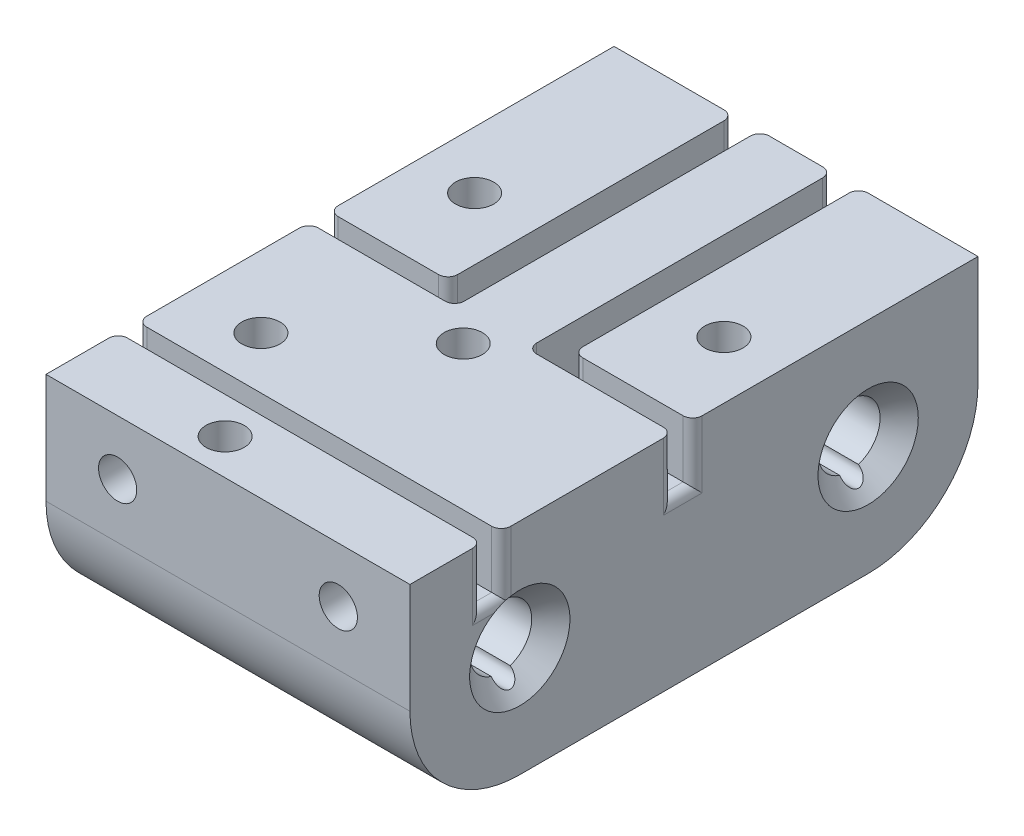
SolidWorks part; units mm, degrees
ref_plane "Front Plane" through (0, 0, 0) normal (0, 0, 1) x (1, 0, 0)
ref_plane "Top Plane" through (0, 0, 0) normal (0, 1, 0) x (1, 0, 0)
ref_plane "Right Plane" through (0, 0, 0) normal (1, 0, 0) x (0, 0, -1)
sketch "Sketch1" plane through (0, 0, 0) normal (1, 0, 0) x (0, 0, -1)
  line L0 (-18.235, 0) -> (18.235, 0)
  line L1 (0, 0) -> (0, -11.9416) construction
  line L3 (-29.735, 11.5) -> (29.735, 11.5)
  line L4 (-29.735, 11.5) -> (-29.735, 0)
  line L5 (-29.735, 0) -> (29.735, 0)
  line L6 (29.735, 11.5) -> (29.735, 0)
  circle A0 centre (-18.235, 0) radius 3.25
  circle A2 centre (-18.235, 0) radius 11.5
  circle A3 centre (18.235, 0) radius 3.25
  circle A4 centre (18.235, 0) radius 11.5
  point P2 (0, 0)
  point P14 (0, 0)
  point P15 (0, 0)
  dimension "D2" = 6.5
  dimension "D3" = 23
  dimension "D1" = 36.47
  dimension "D4" = 59.47
extrude "Boss-Extrude1" add sketch "Sketch1" along normal blind 38.1 contours A4 L5 A3 | A4 L5 A3 | L5 A2 A0 | L5 A2 A0 | L0 L5 A4 L3 A2 | L3 A4 L6 | A2 L3 L4 region at (0, 5.1847, 18.235) region at (0, -5.1847, 18.235) region at (0, 6.6031, 0) region at (0, 8.9313, 27.1663) region at (0, 5.1847, -18.235) region at (0, -5.1847, -18.235) region at (0, 8.9313, -27.1663)
ref_plane "Plane1" through (0, -11.5, 0) normal (0, -1, 0) x (-1, 0, 0)
sketch "Sketch2" plane through (0, -11.5, 0) normal (0, -1, 0) x (-1, 0, 0)
  line L0 (-38.1, 29.735) -> (-38.1, 6.735) construction
  line L1 (-38.1, 18.235) -> (0, 18.235)
  line L2 (-38.1, 18.235) -> (-38.1, -18.235)
  line L3 (-38.1, -18.235) -> (0, -18.235)
  line L4 (0, 18.235) -> (0, -18.235)
  line L5 (0, -29.735) -> (0, -6.735) construction
extrude "Boss-Extrude2" add sketch "Sketch2" against normal up to next
sketch "Sketch3" plane through (0, 11.5, 0) normal (0, 1, 0) x (1, 0, 0)
  line L0 (0, 29.735) -> (38.1, 29.735) construction
  line L1 (0, -0.14) -> (12.5, -0.14)
  line L2 (12.5, -0.14) -> (12.5, 29.735)
  line L3 (15.26, 29.735) -> (15.26, -2.21)
  line L4 (15.26, -2.21) -> (0, -2.21)
  line L5 (19.05, -12.535) -> (19.05, 29.735) construction
  line L6 (0, -1.1775) -> (38.1, -1.1775) construction
  line L7 (22.84, -2.21) -> (38.1, -2.21)
  line L8 (22.84, 29.735) -> (22.84, -2.21)
  line L9 (25.6, -0.14) -> (25.6, 29.735)
  line L10 (38.1, -0.14) -> (25.6, -0.14)
  line L11 (0, 29.735) -> (38.1, 29.735)
  line L12 (0, 29.735) -> (0, -12.535)
  line L13 (0, -12.535) -> (38.1, -12.535)
  line L14 (38.1, 29.735) -> (38.1, -12.535)
  line L15 (0, -2.21) -> (0, -12.535) construction
  line L16 (38.1, 29.735) -> (0, 29.735) construction
  line L17 (0, -29.735) -> (0, 29.735) construction
  line L18 (38.1, -29.735) -> (38.1, 29.735) construction
  line L19 (0, -20.1775) -> (38.1, -20.1775)
  line L20 (0, -20.1775) -> (0, -22.1775)
  line L21 (0, -22.1775) -> (38.1, -22.1775)
  line L22 (38.1, -20.1775) -> (38.1, -22.1775)
  line L23 (0, -21.1775) -> (38.1, -21.1775) construction
  line M5 (0, 29.735) -> (0, -29.735)
  line M7 (38.1, -29.735) -> (38.1, 29.735)
  line M8 (38.1, 29.735) -> (0, 29.735)
  dimension "D1" = 10.325
  dimension "D2" = 12.395
  dimension "D3" = 12.5
  dimension "D4" = 15.26
  dimension "D5" = 1.0375
  dimension "D6" = 38.1
  dimension "D7" = 42.27
  dimension "D8" = 2
  dimension "D9" = 20
extrude "Cut-Extrude1" cut sketch "Sketch3" against normal blind 6 contours L10 L9 L8 L7 M7 M8 | L4 L3 L2 L1 M8 M5 | L19 L22 L21 L20 region at (6.25, 11.5, 0.494) region at (24.22, 11.5, -29.381)
sketch "Sketch4" plane through (0, 11.5, 0) normal (0, 1, 0) x (1, 0, 0)
  line L0 (19.05, 29.735) -> (19.05, -10.265) construction
  line L1 (0, 29.735) -> (38.1, 29.735)
  line L2 (0, 29.735) -> (0, -10.265)
  line L3 (0, -10.265) -> (38.1, -10.265)
  line L4 (38.1, 29.735) -> (38.1, -10.265)
  line L5 (0, -29.735) -> (15, -29.735)
  line L6 (0, -29.735) -> (0, -14.735)
  line L7 (0, -14.735) -> (15, -14.735)
  line L8 (15, -29.735) -> (15, -14.735)
  line L9 (0, -0.14) -> (0, 29.735) construction
  line L10 (38.1, -29.735) -> (0, -29.735) construction
  circle A0 centre (19.05, -5.105) radius 2
  circle A1 centre (6, 9.135) radius 2
  circle A2 centre (32.1, 9.135) radius 2
  circle A3 centre (15, -25.985) radius 2
  circle A4 centre (7.5, -14.735) radius 2
  point P20 (0, 29.735)
  point P22 (1.009, 28.3457)
  point P24 (0, -29.735)
  point P27 (0, -29.735)
  dimension "D4" = 4
  dimension "D9" = 4
  dimension "D10" = 4
  dimension "D1" = 38.1
  dimension "D2" = 5.16
  dimension "D3" = 6
  dimension "D5" = 19.4
  dimension "D6" = 40
  dimension "D7" = 15
  dimension "D8" = 15
  dimension "D11" = 3.75
extrude "Cut-Extrude2" cut sketch "Sketch4" against normal blind 5 contours A1 | A2 | L7 A4 | L7 A4 | L8 A3 | L8 A3 | A0 region at (14.1512, 11.5, 25.985) region at (15.8488, 11.5, 25.985) region at (7.5, 11.5, 13.8862) region at (7.5, 11.5, 15.5838) region at (6, 11.5, -9.135) region at (32.1, 11.5, -9.135)
chamfer "Chamfer1" distance 2 angle 45 4 edges at (38.1, 0, -21.485) (38.1, 0, 14.985) (0, 0, 14.985) (0, 0, -21.485)
sketch "Sketch5" plane through (0, 0, 0) normal (-1, 0, 0) x (0, 0, 1)
  circle A0 centre (-18.235, -3.25) radius 1
  circle A1 centre (-18.235, 0) radius 3.25 construction
  circle A2 centre (18.235, -3.25) radius 1
  circle A3 centre (18.235, 0) radius 3.25 construction
  dimension "D1" = 2
  dimension "D2" = 2
extrude "Cut-Extrude3" cut sketch "Sketch5" against normal through all
sketch "Sketch6" plane through (0, 0, 29.735) normal (0, 0, 1) x (1, 0, 0)
  line L4 (19.05, 11.5) -> (19.05, 0) construction
  line L5 (0, 11.5) -> (38.1, 11.5)
  line L6 (0, 11.5) -> (0, 0)
  line L7 (0, 0) -> (38.1, 0)
  line L9 (38.1, 11.5) -> (38.1, 0)
  line L10 (0, 5.75) -> (7.5, 5.75)
  circle A2 centre (7.5, 5.75) radius 2
  circle A3 centre (30.6, 5.75) radius 2
  point P10 (0, 0)
  dimension "D2" = 4
  dimension "D1" = 7.5
extrude "Cut-Extrude4" cut sketch "Sketch6" against normal blind 5 contours A2 | A3 region at (7.5, 7.6934, 29.735) region at (30.6, 5.75, 29.735)
fillet "Fillet1" radius 1 22 edges at (25.6, 8.5, -29.735) (24.22, 5.5, -29.735) (22.84, 8.5, -29.735) (15.26, 8.5, -29.735) (12.5, 8.5, -29.735) (13.88, 5.5, -29.735) (25.6, 8.5, 0.14) (22.84, 8.5, 2.21) (12.5, 8.5, 0.14) (15.26, 8.5, 2.21) (38.1, 5.5, 21.1775) (38.1, 8.5, 22.1775) (38.1, 8.5, 20.1775) (38.1, 5.5, 1.175) (38.1, 8.5, 2.21) (38.1, 8.5, 0.14) (0, 8.5, 22.1775) (0, 5.5, 21.1775) (0, 8.5, 20.1775) (0, 5.5, 1.175) (0, 8.5, 2.21) (0, 8.5, 0.14)
